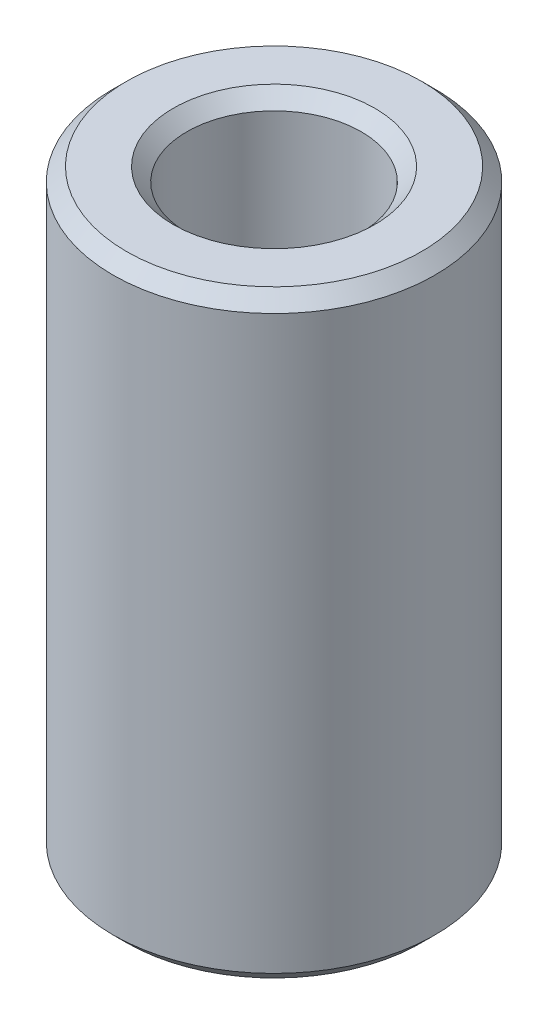
SolidWorks part; units mm, degrees
ref_plane "Front Plane" through (0, 0, 0) normal (0, 0, 1) x (1, 0, 0)
ref_plane "Top Plane" through (0, 0, 0) normal (0, 1, 0) x (1, 0, 0)
ref_plane "Right Plane" through (0, 0, 0) normal (1, 0, 0) x (0, 0, -1)
sketch "Sketch1" plane through (0, 0, 0) normal (0, 1, 0) x (1, 0, 0)
  circle A0 centre (0, 0) radius 12.5
  dimension "SLEEVE_OD" = 25
extrude "Boss-Extrude1" add sketch "Sketch1" along normal blind 46.4537
sketch "Sketch2" plane through (0, 0, 0) normal (0, 1, 0) x (1, 0, 0)
  circle A0 centre (0, 0) radius 6.7716
  dimension "BORE_D" = 13.5432
extrude "Cut-Extrude1" cut sketch "Sketch2" along normal through all
chamfer "Chamfer1" distance 1.0519 angle 45 4 edges at (0, 46.4537, 6.7716) (0, 0, 6.7716) (0, 0, 12.5) (0, 46.4537, 12.5)
